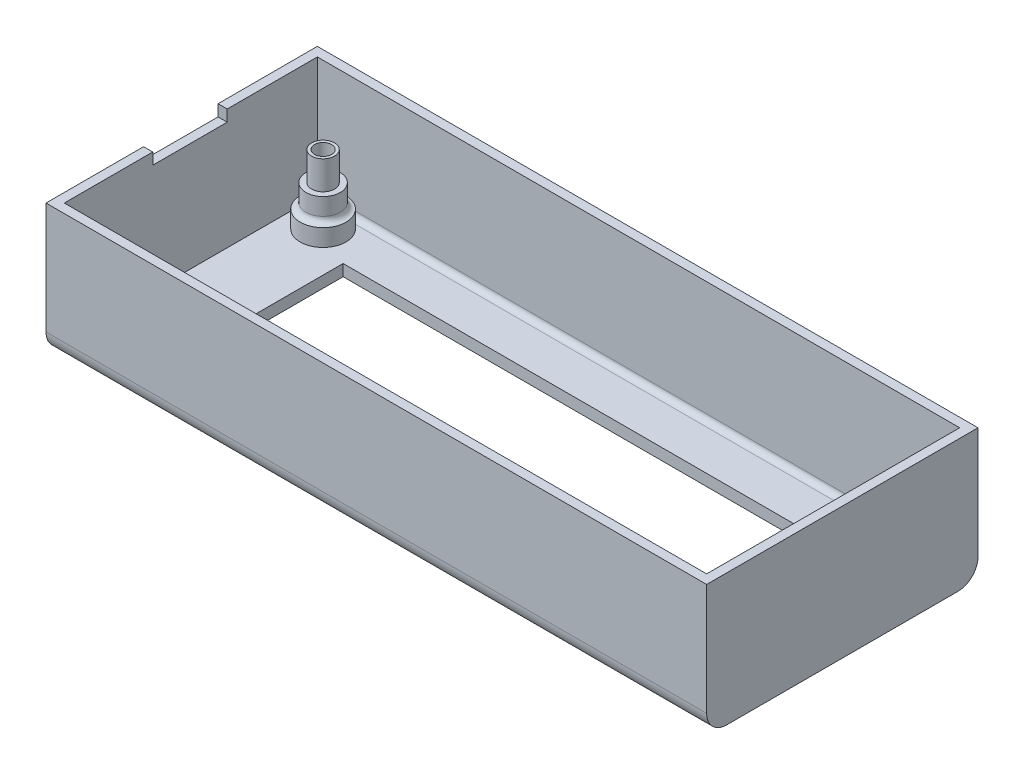
SolidWorks part; units mm, degrees
ref_plane "前视基准面" through (0, 0, 0) normal (0, 0, 1) x (1, 0, 0)
ref_plane "上视基准面" through (0, 0, 0) normal (0, 1, 0) x (1, 0, 0)
ref_plane "右视基准面" through (0, 0, 0) normal (1, 0, 0) x (0, 0, -1)
sketch "草图1" plane through (0, 0, 0) normal (0, 1, 0) x (1, 0, 0)
  line L1 (-57.7, 23.7) -> (57.7, 23.7)
  line L2 (-57.7, 23.7) -> (-57.7, -23.7)
  line L3 (-57.7, -23.7) -> (57.7, -23.7)
  line L4 (57.7, 23.7) -> (57.7, -23.7)
  line L5 (-57.7, 23.7) -> (57.7, -23.7) construction
  line L6 (-57.7, -23.7) -> (57.7, 23.7) construction
  point P0 (0, 0)
  dimension "D1" = 47.4
  dimension "D2" = 115.4
extrude "凸台-拉伸1" add sketch "草图1" along normal blind 2
sketch "草图2" plane through (0, 2, 0) normal (0, 1, 0) x (1, 0, 0)
  line L8 (56.1, -22.1) -> (56.1, 22.1)
  line L9 (56.1, 22.1) -> (-56.1, 22.1)
  line L10 (-56.1, 22.1) -> (-56.1, -22.1)
  line L11 (-56.1, -22.1) -> (56.1, -22.1)
  line L12 (56.1, -22.1) -> (56.1, 22.1)
  line L13 (56.1, 22.1) -> (-56.1, 22.1)
  line L14 (-56.1, 22.1) -> (-56.1, -22.1)
  line L15 (-56.1, -22.1) -> (56.1, -22.1)
  line L24 (57.7, -23.7) -> (57.7, 23.7)
  line L25 (57.7, 23.7) -> (-57.7, 23.7)
  line L26 (-57.7, 23.7) -> (-57.7, -23.7)
  line L27 (-57.7, -23.7) -> (57.7, -23.7)
  line L28 (57.7, -23.7) -> (57.7, 23.7)
  line L29 (57.7, 23.7) -> (-57.7, 23.7)
  line L30 (-57.7, 23.7) -> (-57.7, -23.7)
  line L31 (-57.7, -23.7) -> (57.7, -23.7)
  dimension "D1" = 1.6
  dimension "D2" = 0
extrude "凸台-拉伸2" add sketch "草图2" along normal blind 21
sketch "草图3" plane through (0, 2, 0) normal (0, 1, 0) x (1, 0, 0)
  line L0 (-56.1, 22.1) -> (-56.1, -22.1) construction
  line L1 (43.6, -15.6) -> (-43.6, -15.6)
  line L2 (43.6, -15.6) -> (43.6, 14.1)
  line L3 (43.6, 14.1) -> (-43.6, 14.1)
  line L4 (-43.6, -15.6) -> (-43.6, 14.1)
  line L5 (56.1, -22.1) -> (56.1, 22.1) construction
  line L6 (-56.1, -22.1) -> (56.1, -22.1) construction
  line L7 (56.1, 22.1) -> (-56.1, 22.1) construction
  dimension "D1" = 12.5
  dimension "D2" = 12.5
  dimension "D3" = 6.5
  dimension "D4" = 8
extrude "切除-拉伸1" cut sketch "草图3" against normal up to next
sketch "草图4" plane through (0, 2, 0) normal (0, 1, 0) x (1, 0, 0)
  line L0 (43.6, -15.6) -> (43.6, 14.1) construction
  line L1 (43.6, 6.1) -> (53.6, 6.1)
  line L2 (43.6, 6.1) -> (43.6, 13.1)
  line L3 (43.6, 13.1) -> (53.6, 13.1)
  line L4 (53.6, 6.1) -> (53.6, 13.1)
  line L5 (56.1, 22.1) -> (-56.1, 22.1) construction
  dimension "D1" = 7
  dimension "D2" = 9
  dimension "D3" = 10
extrude "切除-拉伸2" cut sketch "草图4" against normal blind 1.3
sketch "草图5" plane through (0, 2, 0) normal (0, 1, 0) x (1, 0, 0)
  line L0 (-56.1, -22.1) -> (56.1, -22.1) construction
  line L1 (56.1, 22.1) -> (-56.1, 22.1) construction
  line L2 (-56.1, 22.1) -> (-56.1, -22.1) construction
  line L3 (56.1, -22.1) -> (56.1, 22.1) construction
  circle A0 centre (50.6, -17.6) radius 3
  circle A1 centre (50.6, 17.6) radius 3
  circle A2 centre (-50.6, -17.6) radius 3
  circle A3 centre (-50.6, 17.6) radius 3
  dimension "D1" = 4.5
  dimension "D2" = 4.5
  dimension "D3" = 4.5
  dimension "D4" = 4.5
  dimension "D5" = 5.5
  dimension "D6" = 5.5
  dimension "D7" = 5.5
  dimension "D8" = 5.5
extrude "凸台-拉伸3" add sketch "草图5" along normal blind 7
sketch "草图6" plane through (0, 9, 0) normal (0, 1, 0) x (1, 0, 0)
  circle A0 centre (50.6, -17.6) radius 2
  circle A1 centre (50.6, 17.6) radius 2
  circle A2 centre (-50.6, -17.6) radius 2
  circle A3 centre (-50.6, 17.6) radius 2
extrude "凸台-拉伸4" add sketch "草图6" along normal blind 5
sketch "草图7" plane through (0, 14, 0) normal (0, 1, 0) x (1, 0, 0)
  circle A0 centre (50.6, -17.6) radius 1.5
  circle A1 centre (-50.6, -17.6) radius 1.5
  circle A2 centre (50.6, 17.6) radius 1.5
  circle A3 centre (-50.6, 17.6) radius 1.5
extrude "切除-拉伸3" cut sketch "草图7" against normal up to next
sketch "草图8" plane through (0, 2, 0) normal (0, 1, 0) x (1, 0, 0)
  circle A0 centre (50.6, -17.6) radius 4
  circle A1 centre (50.6, 17.6) radius 4
  circle A2 centre (-50.6, -17.6) radius 4
  circle A3 centre (-50.6, 17.6) radius 4
extrude "凸台-拉伸8" add sketch "草图8" along normal blind 3
fillet "圆角1" radius 1 4 edges at (-50.6, 5, -14.6) (-50.6, 5, 20.6) (50.6, 5, -14.6) (50.6, 5, 20.6)
sketch "草图9" plane through (0, 0, 0) normal (0, -1, 0) x (1, 0, 0)
  circle A0 centre (-50.6, 17.6) radius 3
  circle A1 centre (50.6, 17.6) radius 3
  circle A2 centre (50.6, -17.6) radius 3
  circle A3 centre (-50.6, -17.6) radius 3
extrude "切除-拉伸4" cut sketch "草图9" against normal blind 3
sketch "草图10" plane through (0, 5, 0) normal (0, 1, 0) x (1, 0, 0)
  circle A0 centre (50.6, -17.6) radius 1.5
  circle A1 centre (50.6, 17.6) radius 1.5
  circle A2 centre (-50.6, 17.6) radius 1.5
  circle A3 centre (-50.6, -17.6) radius 1.5
extrude "切除-拉伸5" cut sketch "草图10" against normal up to next
sketch "草图11" plane through (0, 23, 0) normal (0, 1, 0) x (1, 0, 0)
  line L0 (-57.7, 23.7) -> (-57.7, -23.7) construction
  line L1 (-57.7, 6.35) -> (-56.1, 6.35)
  line L2 (-57.7, 6.35) -> (-57.7, -6.65)
  line L3 (-57.7, -6.65) -> (-56.1, -6.65)
  line L4 (-56.1, 6.35) -> (-56.1, -6.65)
  line L5 (-56.1, 22.1) -> (-56.1, -22.1) construction
  line L6 (57.7, 23.7) -> (-57.7, 23.7) construction
  line L7 (-57.7, -23.7) -> (57.7, -23.7) construction
  dimension "D1" = 17.35
  dimension "D2" = 17.05
extrude "切除-拉伸6" cut sketch "草图11" against normal blind 2
fillet "圆角2" radius 3.5 2 edges at (0, 0, -23.7) (0, 0, 23.7)
fillet "圆角3" radius 1 2 edges at (0, 2, -22.1) (0, 2, 22.1)
